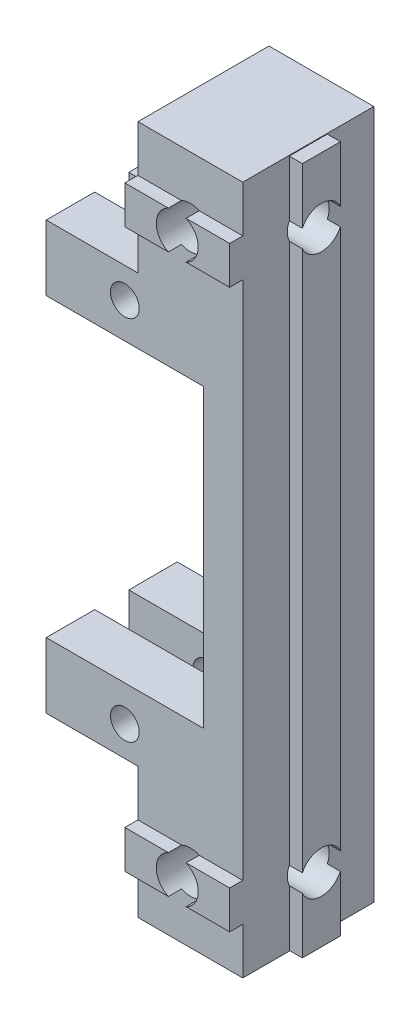
SolidWorks part; units mm, degrees
ref_plane "Front Plane" through (0, 0, 0) normal (0, 0, 1) x (1, 0, 0)
ref_plane "Top Plane" through (0, 0, 0) normal (0, 1, 0) x (1, 0, 0)
ref_plane "Right Plane" through (0, 0, 0) normal (1, 0, 0) x (0, 0, -1)
sketch "Sketch1" plane through (0, 0, 0) normal (0, 0, 1) x (1, 0, 0)
  line L0 (0, 11.3) -> (-12, 11.3)
  line L1 (-12, 11.3) -> (-12, 16.3)
  line L2 (-12, 16.3) -> (-5, 16.3)
  line L3 (3, 26.3) -> (3, -26.3)
  line L4 (-12, -16.3) -> (-5, -16.3)
  line L5 (-12, -16.3) -> (-12, -11.3)
  line L6 (-12, -11.3) -> (0, -11.3)
  line L7 (0, -11.3) -> (0, 11.3)
  line L8 (-6, 14) -> (-6, -14) construction
  line L9 (-5, 16.3) -> (-5, 26.3)
  line L10 (-5, 26.3) -> (3, 26.3)
  line L11 (-5, -16.3) -> (-5, -26.3)
  line L12 (-5, -26.3) -> (3, -26.3)
  circle A0 centre (-6, 14) radius 1.1
  circle A1 centre (-6, -14) radius 1.1
  point P5 (-3.377, 16.3)
  point P10 (0, 0)
  point P12 (-6, -11.3)
  point P15 (-6, 0)
  point P20 (3, -16.3)
  point P22 (3, -23.1894)
  point P23 (-5, 16.3)
  dimension "D5" = 2.2
  dimension "D1" = 22.6
  dimension "D2" = 12
  dimension "D3" = 3
  dimension "D4" = 5
  dimension "D6" = 28
  dimension "D7" = 10
  dimension "D8" = 8
extrude "Main" add sketch "Sketch1" along normal mid plane 10
sketch "Sketch2" plane through (0, 0, 0) normal (0, 1, 0) x (1, 0, 0)
  line L0 (3, -5) -> (3, 5) construction
  line L1 (3, 1.45) -> (4, 1.45)
  line L2 (3, 1.45) -> (3, -1.45)
  line L3 (3, -1.45) -> (4, -1.45)
  line L4 (4, 1.45) -> (4, -1.45)
  line L5 (3, -5) -> (-5, -5) construction
  dimension "D1" = 1
  dimension "D2" = 2.9
  dimension "D3" = 3.55
extrude "MakerBeamSupport" add sketch "Sketch2" along normal mid plane 52.5
sketch "Sketch3" plane through (-5, 0, 0) normal (-1, 0, 0) x (0, 0, 1)
  line L1 (0, -55) -> (0, 55) construction
  line L3 (-5, 26.3) -> (-5, 16.3) construction
  line L4 (-5, -16.3) -> (-5, -26.3) construction
  circle A0 centre (0, 21.3) radius 1.6
  circle A1 centre (0, -21.3) radius 1.6
  point P4 (0, 0)
  point P5 (-5, 21.3)
  point P6 (-5, -21.3)
  dimension "D1" = 3.2
extrude "MakerBeamHoles" cut sketch "Sketch3" against normal through all
sketch "Sketch4" plane through (-12, 0, 0) normal (-1, 0, 0) x (0, 0, 1)
  line L0 (5, 16.3) -> (-5, 16.3) construction
  line L1 (-1.3, 16.3) -> (1.3, 16.3)
  line L2 (-1.3, 16.3) -> (-1.3, -16.3)
  line L3 (-1.3, -16.3) -> (1.3, -16.3)
  line L4 (1.3, 16.3) -> (1.3, -16.3)
  line L5 (5, -16.3) -> (-5, -16.3) construction
  line L7 (-5, 16.3) -> (-5, 11.3) construction
  line L8 (5, 16.3) -> (5, 11.3) construction
  dimension "D1" = 2.6
  dimension "D2" = 3.7
  dimension "D3" = 3.7
extrude "Cut-Extrude2" cut sketch "Sketch4" against normal up to surface (12 mm away) up to face at (0, 0, 0)
sketch "Sketch5" plane through (0, 0, 5) normal (0, 0, -1) x (-1, 0, 0)
  line L1 (-3, 22.75) -> (5, 22.75)
  line L2 (-3, 22.75) -> (-3, 19.85)
  line L3 (-3, 19.85) -> (5, 19.85)
  line L4 (5, 22.75) -> (5, 19.85)
  line L7 (5, -19.85) -> (-3, -19.85)
  line L8 (5, -19.85) -> (5, -22.75)
  line L9 (5, -22.75) -> (-3, -22.75)
  line L10 (-3, -19.85) -> (-3, -22.75)
  line L13 (5, 26.3) -> (5, 16.3) construction
  line L15 (-3, -26.3) -> (-3, 26.3) construction
  line L16 (-3, 26.3) -> (5, 26.3) construction
  line L17 (5, -26.3) -> (-3, -26.3) construction
  line L18 (5, 16.3) -> (12, 16.3) construction
  point P4 (-4, 19.563)
  point P5 (-3, 20.3429)
  point P7 (5, 17.3152)
  point P12 (5, -17.6358)
  point P13 (5, -20.6194)
  point P14 (0, 0)
  dimension "D1" = 2.9
  dimension "D2" = 3.55
  dimension "D3" = 0
  dimension "D4" = 3.55
  dimension "D5" = 3.55
extrude "MakerBeamTopSupport" add sketch "Sketch5" against normal blind 1
sketch "Sketch6" plane through (0, 0, 6) normal (0, 0, 1) x (1, 0, 0)
  line L6 (3, 26.3) -> (-5, 26.3) construction
  line L9 (-5, 19.85) -> (-5, 22.75) construction
  line L11 (-5, -22.75) -> (-5, -19.85) construction
  circle A0 centre (-1, 21.3) radius 1.6
  circle A1 centre (-1, -21.3) radius 1.6
  point P4 (0, 0)
  point P5 (-5, 21.3)
  point P6 (0, 0)
  point P9 (-5, -21.3)
  point P10 (0, 0)
  point P11 (0, 0)
  point P13 (-1, 26.3)
  point P18 (0, 0)
  dimension "D1" = 3.2
extrude "MakerBeamTopHolesSupport" cut sketch "Sketch6" against normal through all
